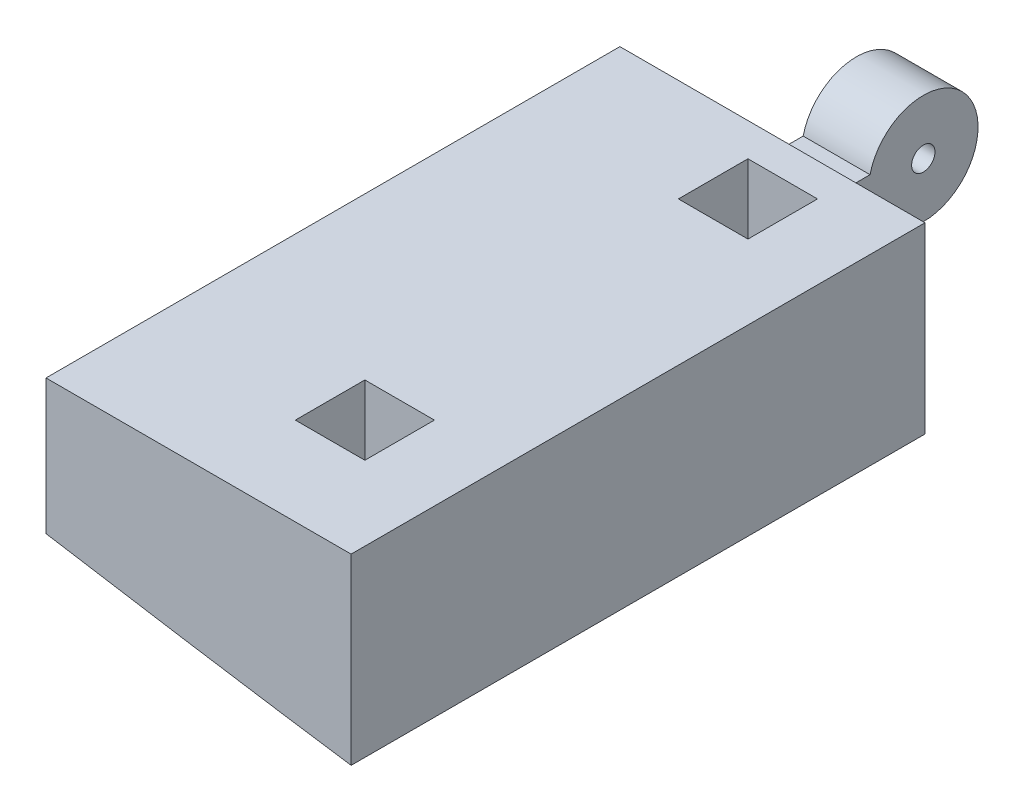
SolidWorks part; units mm, degrees
material "ABS"
ref_plane "Front Plane" through (0, 0, 0) normal (0, 0, 1) x (1, 0, 0)
ref_plane "Top Plane" through (0, 0, 0) normal (0, 1, 0) x (1, 0, 0)
ref_plane "Right Plane" through (0, 0, 0) normal (1, 0, 0) x (0, 0, -1)
sketch "Sketch2" plane through (0, 0, 0) normal (0, 1, 0) x (1, 0, 0)
  line L0 (0, 0) -> (-152.4, 0)
  line L1 (-152.4, 0) -> (-152.4, -152.4)
  line L2 (-152.4, -152.4) -> (0, -152.4)
  line L3 (0, -152.4) -> (0, 0)
  dimension "D1" = 152.4
  dimension "D2" = 152.4
extrude "Boss-Extrude2" add sketch "Sketch2" along normal blind 12.7
ref_plane "Plane2" through (-14.9327, 0, 0) normal (1, 0, 0) x (0, 0, -1)
ref_plane "Plane1" through (-12.7, 0, 0) normal (1, 0, 0) x (0, 0, -1)
sketch "Sketch9" plane through (0, 12.7, 0) normal (0, 1, 0) x (1, 0, 0)
  line L0 (0, 0) -> (0, -48.862) construction
  line L1 (0, -152.4) -> (0, 0) construction
  line L2 (-152.4, 0) -> (-152.4, -48.862) construction
  line L3 (-152.4, 0) -> (-152.4, -152.4) construction
  line L4 (0, 0) -> (-5.4077, 0) construction
  line L5 (0, 0) -> (-152.4, 0) construction
  dimension "D1" = 48.862
  dimension "D2" = 48.862
  dimension "D3" = 5.4077
ref_axis "Axis2" through (-152.4, 12.7, 48.862) along (1, 0, 0)
sketch "Sketch3" plane through (-12.7, 0, 0) normal (1, 0, 0) x (0, 0, -1)
  line L0 (0, 6.35) -> (0, 0)
  line L2 (0, 12.7) -> (0, 0) construction
  line L3 (0, 0) -> (12.7, 0)
  line L4 (12.7, 6.1562) -> (12.7, 6.1587)
  line L5 (7.6839, 6.35) -> (0, 6.35)
  arc A3 (12.7, 0) -> (7.6839, 6.35) centre (12.7, 5.1562) ccw
  circle A5 centre (12.7, 5.1562) radius 1
  dimension "D3" = 10.3124
  dimension "D2" = 0
  dimension "D4" = 7.6839
  dimension "D6" = 2
  dimension "D1" = 6.35
  dimension "D5" = 12.7
extrude "Boss-Extrude3" add sketch "Sketch3" against normal blind 6.3 contours A5 L4 L3 A3 | A5 L4 A3 L3 | A3 L5 L0 L3 region at (-12.7, 4.2781, -9.3369)
ref_plane "Plane5" through (0, 0, 24.431) normal (0, 0, -1) x (-1, 0, 0)
ref_plane "Plane6" through (0, 12.7, 0) normal (0, 1, 0) x (1, 0, 0)
sketch "Sketch10" plane through (0, 12.7, 0) normal (0, 1, 0) x (1, 0, 0)
  line L0 (0, 0) -> (-152.4, 0) construction
  circle A0 centre (-10.2337, -3.175) radius 0.508
  dimension "D1" = 10.2337
  dimension "D3" = 1.016
  dimension "D2" = 3.175
extrude "Cut-Extrude3" [suppressed] cut sketch "Sketch10" against normal blind 9.525
mirror "Mirror1" [suppressed] about plane through (0, 0, 24.431) normal (0, 0, -1)
fillet "Fillet1" radius 1.5875 3 edges at (-19, 3.175, 0) (-15.85, 6.35, 0) (-12.7, 3.175, 0)
pattern_linear "LPattern1" count 4 spacing 41.275 along (-1, 0, 0) of "Boss-Extrude3", "Mirror1", "Fillet1"
sketch "Sketch12" plane through (0, 0, 0) normal (0, 0, -1) x (-1, 0, 0)
  spline S0 degree 1 poles (0, 0) (152.4, 0) knots 0 0 1 1
  spline S1 degree 2 poles (152.4, 0) (-0.2287, -25.399) (0, 0) knots 0 0 0 0.553499 0.553499 0.553499
  spline S2 degree 1 poles (0, 0) (152.4, 0) knots 0 0 1 1
  spline S3 degree 1 poles (152.4, 0) (0, 0) knots 0 0 1 1
  dimension "D1" = 50.8
extrude "Boss-Extrude4" add sketch "Sketch12" against normal up to surface (152.4 mm away) contours S1 | S0 S1 up to face at (-76.2, 6.35, 152.4)
sketch "Sketch13" plane through (0, 12.7, 0) normal (0, 1, 0) x (1, 0, 0)
  line L0 (0, -152.4) -> (0, 0) construction
  line L1 (-81.8426, -69.85) -> (-19.05, -69.85)
  line L2 (-81.8426, -69.85) -> (-81.8426, -96.44)
  line L3 (-81.8426, -96.44) -> (-19.05, -96.44)
  line L4 (-19.05, -69.85) -> (-19.05, -96.44)
  line L5 (0, 0) -> (-152.4, 0) construction
  line L7 (-85.0176, -66.675) -> (-15.875, -66.675)
  line L8 (-85.0176, -66.675) -> (-85.0176, -99.615)
  line L9 (-85.0176, -99.615) -> (-15.875, -99.615)
  line L10 (-15.875, -66.675) -> (-15.875, -99.615)
  dimension "D1" = 62.7926
  dimension "D2" = 26.59
  dimension "D3" = 19.05
  dimension "D4" = 69.85
  dimension "D5" = 3.175
  dimension "D6" = 3.175
  dimension "D7" = 3.175
  dimension "D8" = 3.175
extrude "Boss-Extrude5" add sketch "Sketch13" along normal blind 3.5001
sketch "Sketch14" plane through (0, 12.7, 0) normal (0, 1, 0) x (1, 0, 0)
  line L0 (-19.05, -69.85) -> (-81.8426, -69.85) construction
  line L1 (-81.8426, -69.85) -> (-81.8426, -96.44) construction
  circle A0 centre (-78.1761, -74.1223) radius 1.2497
  circle A1 centre (-22.1767, -74.1223) radius 1.2497
  circle A2 centre (-78.1761, -93.1215) radius 1.2497
  circle A3 centre (-22.1767, -93.1215) radius 1.2497
  dimension "D1" = 4.2723
  dimension "D3" = 3.6665
  dimension "D4" = 55.9994
  dimension "D2" = 18.9992
extrude "Cut-Extrude5" cut sketch "Sketch14" against normal blind 6.35
sketch "Sketch15" plane through (0, 12.7, 0) normal (0, 1, 0) x (1, 0, 0)
  line L0 (-101.6, -152.4) -> (-101.6, -127)
  line L1 (-152.4, -152.4) -> (0, -152.4) construction
  line L2 (-101.6, -127) -> (-152.4, -66.4589)
  line L3 (-152.4, 0) -> (-152.4, -152.4) construction
  line L4 (-152.4, -66.4589) -> (-152.4, -152.4)
  line L5 (-152.4, -152.4) -> (-101.6, -152.4)
  spline S0 degree 3 poles (-101.6, -127) (-102.6273, -119.2728) (-124.8228, -68.0569) (-152.4, -66.4589) knots 0 0 0 0 0.841715 0.841715 0.841715 0.841715
  line M9 (-152.4, 0) -> (-152.4, -152.4)
  line M10 (-152.4, -152.4) -> (0, -152.4)
  dimension "D1" = 50.8
  dimension "D2" = 25.4
  dimension "D3" = 220
extrude "Cut-Extrude6" cut sketch "Sketch15" against normal through all contours L2 S0 | L0 L2 M9 M10 region at (-131.6037, 12.7, 121.8215) region at (-125.8187, 12.7, 91.8783)
sketch "Sketch16" plane through (0, 0, 152.4) normal (0, 0, 1) x (1, 0, 0)
  line L0 (-101.6, 12.7) -> (-101.6, 5.3677)
  line L1 (-101.6, 12.7) -> (-118.0978, 3.175)
  line L2 (-101.6, 5.3677) -> (-118.0978, -4.1573)
  line L3 (-118.0978, 3.175) -> (-118.0978, -4.1573)
  line L4 (-101.6, -7.6022) -> (-101.6, 12.7) construction
  dimension "D1" = 6.35
  dimension "D2" = 60
  dimension "D3" = 19.05
extrude "Boss-Extrude6" add sketch "Sketch16" against normal blind 6.35
sketch "Sketch17" plane through (-27.7243, 48.0198, 0) normal (0.5, -0.866, 0) x (0.866, 0.5, 0)
  line L0 (-104.3544, 146.05) -> (-104.3544, 152.4) construction
  circle A0 centre (-104.3544, 149.225) radius 4.826
  dimension "D1" = 9.652
extrude "Boss-Extrude7" add sketch "Sketch17" against normal up to surface (6.35 mm away) up to face at (-109.8489, 7.9375, 149.225)
sketch "Sketch18" plane through (-27.7243, 48.0198, 0) normal (0.5, -0.866, 0) x (0.866, 0.5, 0)
  circle A0 centre (-104.3544, 149.225) radius 1.143
  dimension "D1" = 2.286
extrude "Cut-Extrude8" cut sketch "Sketch18" against normal up to surface (6.35 mm away) up to face at (-113.8243, 5.6423, 149.225)
ref_plane "Plane7" through (-30.8993, 53.5191, 0) normal (-0.5, 0.866, 0) x (0.866, 0.5, 0)
sketch "Sketch20" plane through (-30.8993, 53.5191, 0) normal (-0.5, 0.866, 0) x (0.866, 0.5, 0)
  line L0 (-86.0567, -130.9381) -> (-86.0567, -143.9239)
  line L1 (-86.0567, -143.9239) -> (-62.911, -143.9239)
  line L2 (-62.911, -143.9239) -> (-62.911, -130.9381)
  line L3 (-62.911, -130.9381) -> (-86.0567, -130.9381)
  dimension "D1" = 12.9857
  dimension "D2" = 23.1457
extrude "Cut-Extrude9" cut sketch "Sketch20" against normal blind 15.494
sketch "Sketch21" plane through (-30.8993, 53.5191, 0) normal (-0.5, 0.866, 0) x (0.866, 0.5, 0)
  line L0 (-86.0373, -130.9653) -> (-90.8633, -130.9653)
  line L1 (-90.8633, -130.9653) -> (-90.8633, -143.951)
  line L2 (-90.8633, -143.951) -> (-86.0373, -143.951)
  line L3 (-86.0373, -143.951) -> (-86.0373, -130.9653)
  line L4 (-63.2251, -143.7536) -> (-58.3991, -143.7536)
  line L5 (-58.3991, -143.7536) -> (-58.3991, -130.7678)
  line L6 (-58.3991, -130.7678) -> (-63.2251, -130.7678)
  line L7 (-63.2251, -130.7678) -> (-63.2251, -143.7536)
  line L8 (6.35, -152.4) -> (6.35, 0) construction
  dimension "D1" = 12.9857
  dimension "D2" = 12.9857
  dimension "D3" = 4.826
  dimension "D4" = 22.8122
  dimension "D5" = 4.826
  dimension "D6" = 64.7491
extrude "Boss-Extrude8" add sketch "Sketch21" against normal up to surface (18.2883 mm away) up to face at (-89.3913, -1.865, 79.9708)
sketch "Sketch22" plane through (-30.8993, 53.5191, 0) normal (-0.5, 0.866, 0) x (0.866, 0.5, 0)
  circle A0 centre (-88.4503, -137.587) radius 0.508
  circle A1 centre (-60.8121, -137.587) radius 0.508
  dimension "D1" = 1.016
  dimension "D2" = 1.016
extrude "Cut-Extrude10" cut sketch "Sketch22" against normal blind 10.16
sketch "Esquisse1" plane through (0, 0, 152.4) normal (0, 0, 1) x (1, 0, 0)
  line L0 (-78.1, 4.563) -> (-78.1, 7.7177)
  line L1 (-74.3, 4.1474) -> (-74.3, 7.7177)
  line L2 (-78.1, 4.563) -> (-92.8263, 3.2599)
  line L3 (-92.8263, -0.7245) -> (-78.1, -2.0277)
  line L4 (-78.1, -2.0277) -> (-78.1, -5.1823)
  line L5 (-74.3, -5.1823) -> (-74.3, -1.612)
  line L6 (-73.9909, -1.3823) -> (-62.0409, -0.7293)
  line L7 (-73.9909, 3.9177) -> (-62.0409, 3.2647)
  arc A0 (-78.1, 7.7177) -> (-74.3, 7.7177) centre (-76.2, 7.7177) cw
  arc A2 (-62.0409, 3.2647) -> (-62.0409, -0.7293) centre (-62.15, 1.2677) cw
  arc A3 (-92.8263, 3.2599) -> (-92.8263, -0.7245) centre (-92.65, 1.2677) ccw
  arc A4 (-78.1, -5.1823) -> (-74.3, -5.1823) centre (-76.2, -5.1823) ccw
  arc A5 (-74.3, 4.1474) -> (-73.9909, 3.9177) centre (-76.2, 1.2677) cw
  arc A6 (-73.9909, -1.3823) -> (-74.3, -1.612) centre (-76.2, 1.2677) cw
extrude "Enlèv. mat.-Extru.2" cut sketch "Esquisse1" against normal blind 2.54
hole_wizard "Dégagement #00001" positions "Esquisse2" profile "Esquisse3" hole size "#0000" standard "Ansi Inch"
sketch "Esquisse2" plane through (0, 0, 149.86) normal (0, 0, 1) x (1, 0, 0)
  point P17 (-76.2, 7.7168)
  point P19 (-61.7499, 1.2677)
  point P21 (-76.2, -5.1814)
  dimension "D3" = 0
  dimension "D4" = 6.4491
  dimension "D5" = 0
  dimension "D6" = 6.4491
  dimension "D7" = 0
  dimension "D8" = 14.4501
sketch "Esquisse3" plane through (-76.2, 7.7168, 149.86) normal (1, 0, 0) x (0, -1, 0)
  line L0 (0, 0) -> (0, 9.652)
  line L1 (0, 9.652) -> (0.5994, 9.652)
  line L2 (0.5994, 9.652) -> (0.5994, 0)
  line L5 (0.5994, 0) -> (0, 0)
  line L10 (0, 9.652) -> (-0.5994, 9.652) construction
  line L11 (0, -6.35) -> (0, 107.95) construction
  dimension "Diamètre du perçage" = 1.1989
  dimension "Profondeur du perçage" = 9.652
  dimension "Angle de pointe" = 180
fillet "Fillet2" radius 6.35 2 edges at (-101.6, 2.5489, 127) (-152.4, 6.35, 66.4589)
sketch "Sketch23" plane through (-50.5751, -29.1996, 0) normal (0.866, 0.5, 0) x (0, 0, -1)
  line L0 (-139.1816, 51.8925) -> (-139.1816, 50.3685)
  line L1 (-139.1816, 50.3685) -> (-135.6256, 50.3685)
  line L2 (-135.6256, 50.3685) -> (-135.6256, 51.8925)
  line L3 (-135.6256, 51.8925) -> (-139.1816, 51.8925)
  line L4 (-143.7536, 61.7985) -> (-130.7678, 61.7985) construction
  line L5 (-143.7536, 48.3814) -> (-143.7536, 61.7985) construction
  dimension "D1" = 9.906
  dimension "D2" = 4.572
  dimension "D3" = 3.556
  dimension "D4" = 1.524
extrude "Cut-Extrude11" cut sketch "Sketch23" against normal up to surface (4.826 mm away) up to face at (-81.2997, 14.365, 135.1532)
sketch "Esquisse5" plane through (0, 12.7, 0) normal (0, 1, 0) x (1, 0, 0)
  line L0 (-130.7715, -45.6452) -> (-137.1215, -45.6452) construction
  line L1 (-137.1215, -45.6452) -> (-137.1215, -39.2952) construction
  line L2 (-137.1215, -39.2952) -> (-130.7715, -39.2952) construction
  line L3 (-130.7715, -39.2952) -> (-130.7715, -45.6452) construction
  line L4 (-130.7715, -9.5674) -> (-137.1215, -9.5674) construction
  line L5 (-137.1215, -9.5674) -> (-137.1215, -3.2174) construction
  line L6 (-137.1215, -3.2174) -> (-130.7715, -3.2174) construction
  line L7 (-130.7715, -3.2174) -> (-130.7715, -9.5674) construction
  line L8 (-130.7715, -45.6452) -> (-137.1215, -45.6452) construction
  line L9 (-137.1215, -45.6452) -> (-137.1215, -39.2952) construction
  line L10 (-137.1215, -39.2952) -> (-130.7715, -39.2952) construction
  line L11 (-130.7715, -39.2952) -> (-130.7715, -45.6452) construction
  line L12 (-130.7715, -9.5674) -> (-137.1215, -9.5674) construction
  line L13 (-137.1215, -9.5674) -> (-137.1215, -3.2174) construction
  line L14 (-137.1215, -3.2174) -> (-130.7715, -3.2174) construction
  line L15 (-130.7715, -3.2174) -> (-130.7715, -9.5674) construction
  line L16 (-137.2215, -3.1174) -> (-130.6715, -3.1174)
  line L17 (-130.6715, -3.1174) -> (-130.6715, -9.6674)
  line L18 (-130.6715, -9.6674) -> (-137.2215, -9.6674)
  line L19 (-137.2215, -9.6674) -> (-137.2215, -3.1174)
  line L20 (-137.2215, -39.1952) -> (-130.6715, -39.1952)
  line L21 (-130.6715, -39.1952) -> (-130.6715, -45.7452)
  line L22 (-130.6715, -45.7452) -> (-137.2215, -45.7452)
  line L23 (-137.2215, -45.7452) -> (-137.2215, -39.1952)
  dimension "D1" = 0.1
extrude "Enlèv. mat.-Extru.3" cut sketch "Esquisse5" against normal blind 7.62
sketch "Esquisse6" plane through (0, 12.7, 0) normal (0, 1, 0) x (1, 0, 0)
  line L1 (-159.0109, 20.989) -> (-123.6661, 20.989)
  line L2 (-159.0109, 20.989) -> (-159.0109, -54.0464)
  line L3 (-159.0109, -54.0464) -> (-123.6661, -54.0464)
  line L4 (-123.6661, 20.989) -> (-123.6661, -54.0464)
extrude "Enlèv. mat.-Extru.4" cut sketch "Esquisse6" against normal through all flip side to cut
sketch "Esquisse7" plane through (-136.525, 0, 0) normal (1, 0, 0) x (0, 0, -1)
  circle A0 centre (12.7, 5.1562) radius 1.1
  dimension "D1" = 2.2
extrude "Enlèv. mat.-Extru.5" cut sketch "Esquisse7" against normal through all
